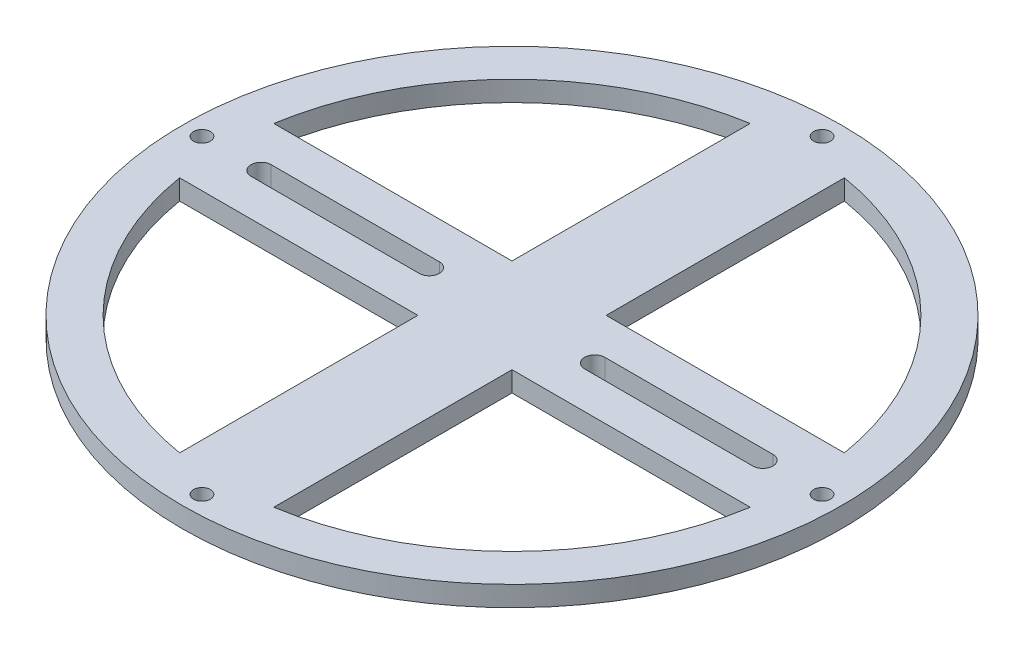
SolidWorks part; units mm, degrees
ref_plane "前视" through (0, 0, 0) normal (0, 0, 1) x (1, 0, 0)
ref_plane "上视" through (0, 0, 0) normal (0, 1, 0) x (1, 0, 0)
ref_plane "右视" through (0, 0, 0) normal (1, 0, 0) x (0, 0, -1)
sketch "草图1" plane through (0, 0, 0) normal (0, 1, 0) x (1, 0, 0)
  line L0 (-66.1799, 0) -> (81.937, 0) construction
  circle A0 centre (0, 0) radius 49
  dimension "D1" = 98
extrude "凸台-拉伸1" add sketch "草图1" along normal blind 3
sketch "草图2" plane through (0, 3, 0) normal (0, 1, 0) x (1, 0, 0)
  line L0 (0, 51.8724) -> (0, -53.4296) construction
  line L1 (-65.7201, 0) -> (62.0667, 0) construction
  circle A1 centre (0, 46.1) radius 1.25
  dimension "D1" = 46.1
  dimension "D2" = 2.5
sketch "草图5" plane through (0, 3, 0) normal (0, 1, 0) x (1, 0, 0)
  line L0 (-59.7985, 0) -> (61.0663, 0) construction
  line L1 (7, -53.9211) -> (7, 55.1109) construction
  line L2 (-63.602, 7) -> (62.9681, 7) construction
  line L4 (7, 42.42) -> (7, 7)
  line L5 (7, 7) -> (42.42, 7)
  arc A0 (7, 42.42) -> (42.42, 7) centre (0, 0) cw
  dimension "D1" = 7
  dimension "D2" = 7
extrude "切除-拉伸3" cut sketch "草图5" against normal through all
sketch "草图6" plane through (0, 3, 0) normal (0, 1, 0) x (1, 0, 0)
  line L0 (-12.3, 0) -> (-37.3, 0) construction
  line L1 (-65.7201, 0) -> (62.0667, 0) construction
  line L2 (-12.3, -1.5) -> (-37.3, -1.5)
  line L3 (-12.3, 1.5) -> (-37.3, 1.5)
  arc A0 (-12.3, -1.5) -> (-12.3, 1.5) centre (-12.3, 0) ccw
  arc A1 (-37.3, 1.5) -> (-37.3, -1.5) centre (-37.3, 0) ccw
  point P4 (-24.8, 0)
  dimension "D1" = 12.3
  dimension "D2" = 25
extrude "切除-拉伸4" cut sketch "草图6" against normal through all
pattern_circular "阵列(圆周)4" count 2 over 360 about axis through (0, 3, 0) along (0, -1, 0) of "切除-拉伸4"
extrude "切除-拉伸5" cut sketch "草图2" against normal through all
pattern_circular "阵列(圆周)5" count 4 over 360 about axis through (0, 3, 0) along (0, -1, 0) of "切除-拉伸5"
sketch "草图7" plane through (0, 3, 0) normal (0, 1, 0) x (1, 0, 0)
  line L0 (24.8, 2.9726) -> (24.8, -3.72) construction
pattern_circular "阵列(圆周)6" count 4 over 360 about axis through (0, 3, 0) along (0, -1, 0) of "切除-拉伸3"
